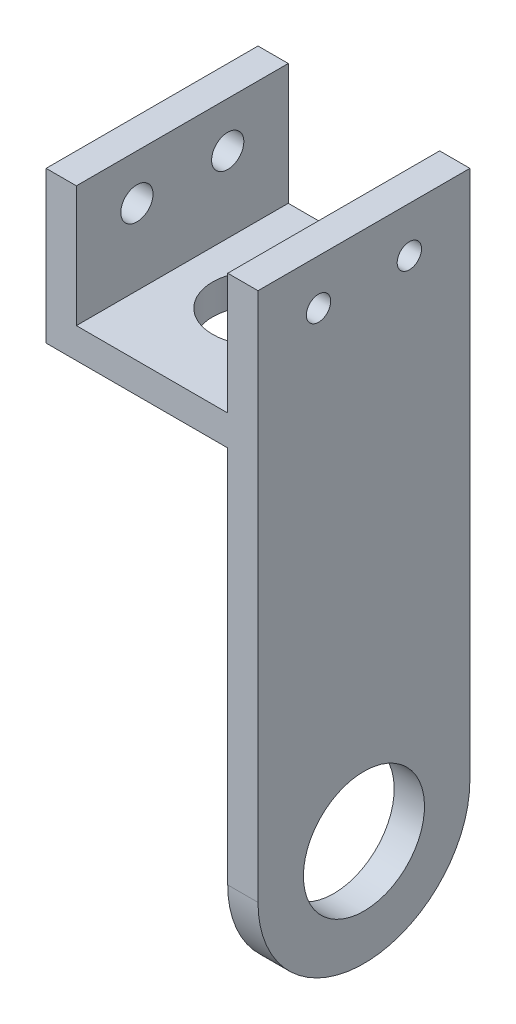
SolidWorks part; units mm, degrees
material "6061-T6 (SS)"
ref_plane "Front" through (0, 0, 0) normal (0, 0, 1) x (1, 0, 0)
ref_plane "Top" through (0, 0, 0) normal (0, 1, 0) x (1, 0, 0)
ref_plane "Right" through (0, 0, 0) normal (1, 0, 0) x (0, 0, -1)
sketch "Sketch1" plane through (0, 0, 0) normal (0, 0, 1) x (1, 0, 0)
  line L0 (0, 0) -> (6.35, 0)
  line L1 (6.35, 0) -> (6.35, 133.35)
  line L2 (6.35, 133.35) -> (0, 133.35)
  line L3 (0, 133.35) -> (0, 107.95)
  line L4 (0, 107.95) -> (-31.75, 107.95)
  line L5 (-31.75, 107.95) -> (-31.75, 133.35)
  line L6 (-31.75, 133.35) -> (-38.1, 133.35)
  line L7 (-38.1, 133.35) -> (-38.1, 101.6)
  line L8 (-38.1, 101.6) -> (0, 101.6)
  line L9 (0, 101.6) -> (0, 0)
  point P3 (3.175, 0)
  dimension "D1" = 6.35
  dimension "D2" = 101.6
  dimension "D3" = 31.75
  dimension "D4" = 6.35
  dimension "D5" = 6.35
  dimension "D6" = 25.4
  dimension "D8" = 6.35
extrude "Boss-Extrude1" add sketch "Sketch1" along normal blind 44.45
sketch "Sketch2" plane through (0, 0, 0) normal (-1, 0, 0) x (0, 0, 1)
  line L0 (44.45, 0) -> (0, 0) construction
  line L1 (44.45, 101.6) -> (44.45, 0) construction
  circle A0 centre (22.225, 22.225) radius 12.7
  dimension "D3" = 25.4
  dimension "D1" = 22.225
  dimension "D2" = 22.225
extrude "Cut-Extrude1" cut sketch "Sketch2" against normal blind 44.45
hole_wizard "1/4-20 Tapped Hole1" positions "Sketch3" profile "Sketch4" tap size "1/4-20" standard "ANSI Inch" end condition through all
sketch "Sketch3" plane through (0, 0, 0) normal (-1, 0, 0) x (0, 0, 1)
  line L2 (44.45, 133.35) -> (0, 133.35) construction
  line L3 (0, 133.35) -> (0, 107.95) construction
  point P0 (12.7, 123.825)
  point P2 (31.75, 123.825)
  dimension "D1" = 19.05
  dimension "D2" = 9.525
  dimension "D3" = 12.7
sketch "Sketch4" plane through (0, 123.825, 12.7) normal (0, 1, 0) x (0, 0, 1)
  line L0 (0, 0) -> (0, 6.35)
  line L1 (0, 6.35) -> (2.5527, 6.35)
  line L2 (2.5527, 6.35) -> (2.5527, 0)
  line L5 (2.5527, 0) -> (0, 0)
  line L11 (0, -6.35) -> (0, 107.95) construction
  dimension "Thru Tap Drill Dia." = 5.1054
  dimension "Thru Tap Drill Depth" = 6.35
cosmetic thread "Hole Thread1" parameters "D2"=6.35
cosmetic thread "Hole Thread2" parameters "D2"=6.35
sketch "Sketch5" plane through (-38.1, 0, 0) normal (-1, 0, 0) x (0, 0, 1)
  line L0 (44.45, 133.35) -> (0, 133.35) construction
  line L1 (44.45, 133.35) -> (44.45, 101.6) construction
  circle A0 centre (12.7, 123.825) radius 3.3782
  circle A1 centre (31.75, 123.825) radius 3.3782
  dimension "D4" = 6.7564
  dimension "D1" = 19.05
  dimension "D2" = 9.525
  dimension "D3" = 12.7
extrude "Cut-Extrude2" cut sketch "Sketch5" against normal blind 8.89
sketch "Sketch6" plane through (0, 107.95, 0) normal (0, 1, 0) x (1, 0, 0)
  line L0 (6.35, -44.45) -> (0, -44.45) construction
  line L2 (0, -44.45) -> (0, 0) construction
  circle A0 centre (-15.875, -22.225) radius 9.525
  dimension "D1" = 19.05
  dimension "D2" = 22.225
  dimension "D3" = 15.875
extrude "Cut-Extrude3" cut sketch "Sketch6" against normal blind 8.89
fillet "Fillet1" 2 edges at (3.175, 0, 44.45) (3.175, 0, 0) type full round first side face at (-12.7, 95.25, 44.45) second side face at (-12.7, 95.25, 0) middle face at (3.175, 0, 22.225)
